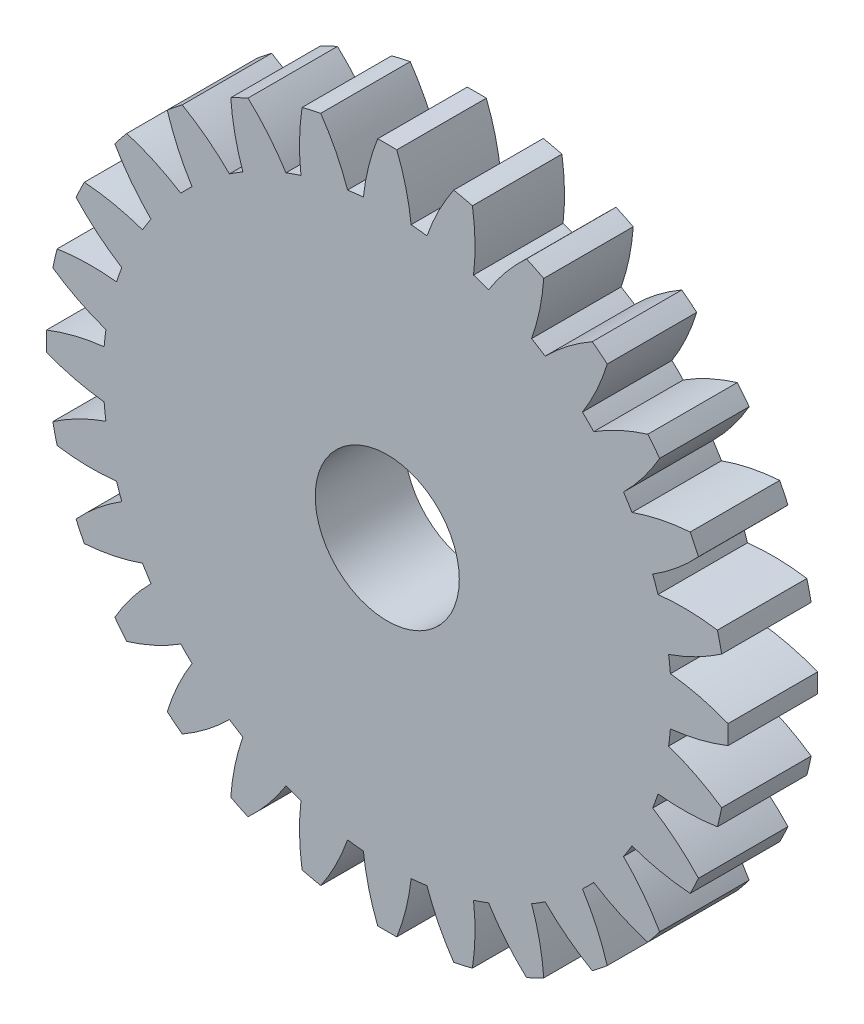
SolidWorks part; units mm, degrees
ref_plane "Front Plane" through (0, 0, 0) normal (0, 0, 1) x (1, 0, 0)
ref_plane "Top Plane" through (0, 0, 0) normal (0, 1, 0) x (1, 0, 0)
ref_plane "Right Plane" through (0, 0, 0) normal (1, 0, 0) x (0, 0, -1)
ref_plane "Plane1" through (0, 0, 5) normal (0, 0, 1) x (1, 0, 0)
sketch "Sketch1" plane through (0, 0, 5) normal (0, 0, 1) x (1, 0, 0)
  line L3 (0, 0) -> (-1.7774, 15.7752) construction
  arc A0 (-4.8209, 15.1253) -> (-5.6614, 14.8312) centre (0, 0) ccw
  arc A1 (-5.6614, 14.8312) -> (-7.7809, 17.3885) centre (-16.2618, 8.2026) ccw
  arc A2 (-7.7809, 17.3885) -> (-8.7436, 16.9249) centre (0, 0) ccw
  arc A3 (-8.7436, 16.9249) -> (-8.0657, 13.6733) centre (3.7261, 17.8282) ccw
  arc A4 (-8.0657, 13.6733) -> (-8.8197, 13.1996) centre (0, 0) ccw
  arc A5 (-8.8197, 13.1996) -> (-11.4551, 15.2211) centre (-17.6794, 4.3783) ccw
  arc A6 (-11.4551, 15.2211) -> (-12.2905, 14.5549) centre (0, 0) ccw
  arc A7 (-12.2905, 14.5549) -> (-10.9061, 11.5357) centre (-0.3345, 18.2104) ccw
  arc A8 (-10.9061, 11.5357) -> (-11.5357, 10.9061) centre (0, 0) ccw
  arc A9 (-11.5357, 10.9061) -> (-14.5549, 12.2905) centre (-18.2104, 0.3345) ccw
  arc A10 (-14.5549, 12.2905) -> (-15.2211, 11.4551) centre (0, 0) ccw
  arc A11 (-15.2211, 11.4551) -> (-13.1996, 8.8197) centre (-4.3783, 17.6794) ccw
  arc A12 (-13.1996, 8.8197) -> (-13.6733, 8.0657) centre (0, 0) ccw
  arc A13 (-13.6733, 8.0657) -> (-16.9249, 8.7436) centre (-17.8282, -3.7261) ccw
  arc A14 (-16.9249, 8.7436) -> (-17.3885, 7.7809) centre (0, 0) ccw
  arc A15 (-17.3885, 7.7809) -> (-14.8312, 5.6614) centre (-8.2026, 16.2618) ccw
  arc A16 (-14.8312, 5.6614) -> (-15.1253, 4.8209) centre (0, 0) ccw
  arc A17 (-15.1253, 4.8209) -> (-18.4462, 4.7582) centre (-16.5521, -7.5998) ccw
  arc A18 (-18.4462, 4.7582) -> (-18.684, 3.7165) centre (0, 0) ccw
  arc A19 (-18.684, 3.7165) -> (-15.7191, 2.2192) centre (-11.6155, 14.0289) ccw
  arc A20 (-15.7191, 2.2192) -> (-15.8188, 1.3343) centre (0, 0) ccw
  arc A21 (-15.8188, 1.3343) -> (-19.0425, 0.5343) centre (-14.446, -11.0924) ccw
  arc A22 (-19.0425, 0.5343) -> (-19.0425, -0.5343) centre (0, 0) ccw
  arc A23 (-19.0425, -0.5343) -> (-15.8188, -1.3343) centre (-14.446, 11.0924) ccw
  arc A24 (-15.8188, -1.3343) -> (-15.7191, -2.2192) centre (0, 0) ccw
  arc A25 (-15.7191, -2.2192) -> (-18.684, -3.7165) centre (-11.6155, -14.0289) ccw
  arc A26 (-18.684, -3.7165) -> (-18.4462, -4.7582) centre (0, 0) ccw
  arc A27 (-18.4462, -4.7582) -> (-15.1253, -4.8209) centre (-16.5521, 7.5998) ccw
  arc A28 (-15.1253, -4.8209) -> (-14.8312, -5.6614) centre (0, 0) ccw
  arc A29 (-14.8312, -5.6614) -> (-17.3885, -7.7809) centre (-8.2026, -16.2618) ccw
  arc A30 (-17.3885, -7.7809) -> (-16.9249, -8.7436) centre (0, 0) ccw
  arc A31 (-16.9249, -8.7436) -> (-13.6733, -8.0657) centre (-17.8282, 3.7261) ccw
  arc A32 (-13.6733, -8.0657) -> (-13.1996, -8.8197) centre (0, 0) ccw
  arc A33 (-13.1996, -8.8197) -> (-15.2211, -11.4551) centre (-4.3783, -17.6794) ccw
  arc A34 (-15.2211, -11.4551) -> (-14.5549, -12.2905) centre (0, 0) ccw
  arc A35 (-14.5549, -12.2905) -> (-11.5357, -10.9061) centre (-18.2104, -0.3345) ccw
  arc A36 (-11.5357, -10.9061) -> (-10.9061, -11.5357) centre (0, 0) ccw
  arc A37 (-10.9061, -11.5357) -> (-12.2905, -14.5549) centre (-0.3345, -18.2104) ccw
  arc A38 (-12.2905, -14.5549) -> (-11.4551, -15.2211) centre (0, 0) ccw
  arc A39 (-11.4551, -15.2211) -> (-8.8197, -13.1996) centre (-17.6794, -4.3783) ccw
  arc A40 (-8.8197, -13.1996) -> (-8.0657, -13.6733) centre (0, 0) ccw
  arc A41 (-8.0657, -13.6733) -> (-8.7436, -16.9249) centre (3.7261, -17.8282) ccw
  arc A42 (-8.7436, -16.9249) -> (-7.7809, -17.3885) centre (0, 0) ccw
  arc A43 (-7.7809, -17.3885) -> (-5.6614, -14.8312) centre (-16.2618, -8.2026) ccw
  arc A44 (-5.6614, -14.8312) -> (-4.8209, -15.1253) centre (0, 0) ccw
  arc A45 (-4.8209, -15.1253) -> (-4.7582, -18.4462) centre (7.5998, -16.5521) ccw
  arc A46 (-4.7582, -18.4462) -> (-3.7165, -18.684) centre (0, 0) ccw
  arc A47 (-3.7165, -18.684) -> (-2.2192, -15.7191) centre (-14.0289, -11.6155) ccw
  arc A48 (-2.2192, -15.7191) -> (-1.3343, -15.8188) centre (0, 0) ccw
  arc A49 (-1.3343, -15.8188) -> (-0.5343, -19.0425) centre (11.0924, -14.446) ccw
  arc A50 (-0.5343, -19.0425) -> (0.5343, -19.0425) centre (0, 0) ccw
  arc A51 (0.5343, -19.0425) -> (1.3343, -15.8188) centre (-11.0924, -14.446) ccw
  arc A52 (1.3343, -15.8188) -> (2.2192, -15.7191) centre (0, 0) ccw
  arc A53 (2.2192, -15.7191) -> (3.7165, -18.684) centre (14.0289, -11.6155) ccw
  arc A54 (3.7165, -18.684) -> (4.7582, -18.4462) centre (0, 0) ccw
  arc A55 (4.7582, -18.4462) -> (4.8209, -15.1253) centre (-7.5998, -16.5521) ccw
  arc A56 (4.8209, -15.1253) -> (5.6614, -14.8312) centre (0, 0) ccw
  arc A57 (5.6614, -14.8312) -> (7.7809, -17.3885) centre (16.2618, -8.2026) ccw
  arc A58 (7.7809, -17.3885) -> (8.7436, -16.9249) centre (0, 0) ccw
  arc A59 (8.7436, -16.9249) -> (8.0657, -13.6733) centre (-3.7261, -17.8282) ccw
  arc A60 (8.0657, -13.6733) -> (8.8197, -13.1996) centre (0, 0) ccw
  arc A61 (8.8197, -13.1996) -> (11.4551, -15.2211) centre (17.6794, -4.3783) ccw
  arc A62 (11.4551, -15.2211) -> (12.2905, -14.5549) centre (0, 0) ccw
  arc A63 (12.2905, -14.5549) -> (10.9061, -11.5357) centre (0.3345, -18.2104) ccw
  arc A64 (10.9061, -11.5357) -> (11.5357, -10.9061) centre (0, 0) ccw
  arc A65 (11.5357, -10.9061) -> (14.5549, -12.2905) centre (18.2104, -0.3345) ccw
  arc A66 (14.5549, -12.2905) -> (15.2211, -11.4551) centre (0, 0) ccw
  arc A67 (15.2211, -11.4551) -> (13.1996, -8.8197) centre (4.3783, -17.6794) ccw
  arc A68 (13.1996, -8.8197) -> (13.6733, -8.0657) centre (0, 0) ccw
  arc A69 (13.6733, -8.0657) -> (16.9249, -8.7436) centre (17.8282, 3.7261) ccw
  arc A70 (16.9249, -8.7436) -> (17.3885, -7.7809) centre (0, 0) ccw
  arc A71 (17.3885, -7.7809) -> (14.8312, -5.6614) centre (8.2026, -16.2618) ccw
  arc A72 (14.8312, -5.6614) -> (15.1253, -4.8209) centre (0, 0) ccw
  arc A73 (15.1253, -4.8209) -> (18.4462, -4.7582) centre (16.5521, 7.5998) ccw
  arc A74 (18.4462, -4.7582) -> (18.684, -3.7165) centre (0, 0) ccw
  arc A75 (18.684, -3.7165) -> (15.7191, -2.2192) centre (11.6155, -14.0289) ccw
  arc A76 (15.7191, -2.2192) -> (15.8188, -1.3343) centre (0, 0) ccw
  arc A77 (15.8188, -1.3343) -> (19.0425, -0.5343) centre (14.446, 11.0924) ccw
  arc A78 (19.0425, -0.5343) -> (19.0425, 0.5343) centre (0, 0) ccw
  arc A79 (19.0425, 0.5343) -> (15.8188, 1.3343) centre (14.446, -11.0924) ccw
  arc A80 (15.8188, 1.3343) -> (15.7191, 2.2192) centre (0, 0) ccw
  arc A81 (15.7191, 2.2192) -> (18.684, 3.7165) centre (11.6155, 14.0289) ccw
  arc A82 (18.684, 3.7165) -> (18.4462, 4.7582) centre (0, 0) ccw
  arc A83 (18.4462, 4.7582) -> (15.1253, 4.8209) centre (16.5521, -7.5998) ccw
  arc A84 (15.1253, 4.8209) -> (14.8312, 5.6614) centre (0, 0) ccw
  arc A85 (14.8312, 5.6614) -> (17.3885, 7.7809) centre (8.2026, 16.2618) ccw
  arc A86 (17.3885, 7.7809) -> (16.9249, 8.7436) centre (0, 0) ccw
  arc A87 (16.9249, 8.7436) -> (13.6733, 8.0657) centre (17.8282, -3.7261) ccw
  arc A88 (13.6733, 8.0657) -> (13.1996, 8.8197) centre (0, 0) ccw
  arc A89 (13.1996, 8.8197) -> (15.2211, 11.4551) centre (4.3783, 17.6794) ccw
  arc A90 (15.2211, 11.4551) -> (14.5549, 12.2905) centre (0, 0) ccw
  arc A91 (14.5549, 12.2905) -> (11.5357, 10.9061) centre (18.2104, 0.3345) ccw
  arc A92 (11.5357, 10.9061) -> (10.9061, 11.5357) centre (0, 0) ccw
  arc A93 (10.9061, 11.5357) -> (12.2905, 14.5549) centre (0.3345, 18.2104) ccw
  arc A94 (12.2905, 14.5549) -> (11.4551, 15.2211) centre (0, 0) ccw
  arc A95 (11.4551, 15.2211) -> (8.8197, 13.1996) centre (17.6794, 4.3783) ccw
  arc A96 (8.8197, 13.1996) -> (8.0657, 13.6733) centre (0, 0) ccw
  arc A97 (8.0657, 13.6733) -> (8.7436, 16.9249) centre (-3.7261, 17.8282) ccw
  arc A98 (8.7436, 16.9249) -> (7.7809, 17.3885) centre (0, 0) ccw
  arc A99 (7.7809, 17.3885) -> (5.6614, 14.8312) centre (16.2618, 8.2026) ccw
  arc A100 (5.6614, 14.8312) -> (4.8209, 15.1253) centre (0, 0) ccw
  arc A101 (4.8209, 15.1253) -> (4.7582, 18.4462) centre (-7.5998, 16.5521) ccw
  arc A102 (4.7582, 18.4462) -> (3.7165, 18.684) centre (0, 0) ccw
  arc A103 (3.7165, 18.684) -> (2.2192, 15.7191) centre (14.0289, 11.6155) ccw
  arc A104 (2.2192, 15.7191) -> (1.3343, 15.8188) centre (0, 0) ccw
  arc A105 (1.3343, 15.8188) -> (0.5343, 19.0425) centre (-11.0924, 14.446) ccw
  arc A106 (0.5343, 19.0425) -> (-0.5343, 19.0425) centre (0, 0) ccw
  arc A107 (-0.5343, 19.0425) -> (-1.3343, 15.8188) centre (11.0924, 14.446) ccw
  arc A108 (-1.3343, 15.8188) -> (-2.2192, 15.7191) centre (0, 0) ccw
  arc A109 (-2.2192, 15.7191) -> (-3.7165, 18.684) centre (-14.0289, 11.6155) ccw
  arc A110 (-3.7165, 18.684) -> (-4.7582, 18.4462) centre (0, 0) ccw
  arc A111 (-4.7582, 18.4462) -> (-4.8209, 15.1253) centre (7.5998, 16.5521) ccw
  circle A112 centre (0, 0) radius 4.025
  dimension "D2" = 8.05
  dimension "D1" = 19.05
extrude "Boss-Extrude1" add sketch "Sketch1" against normal blind 5
